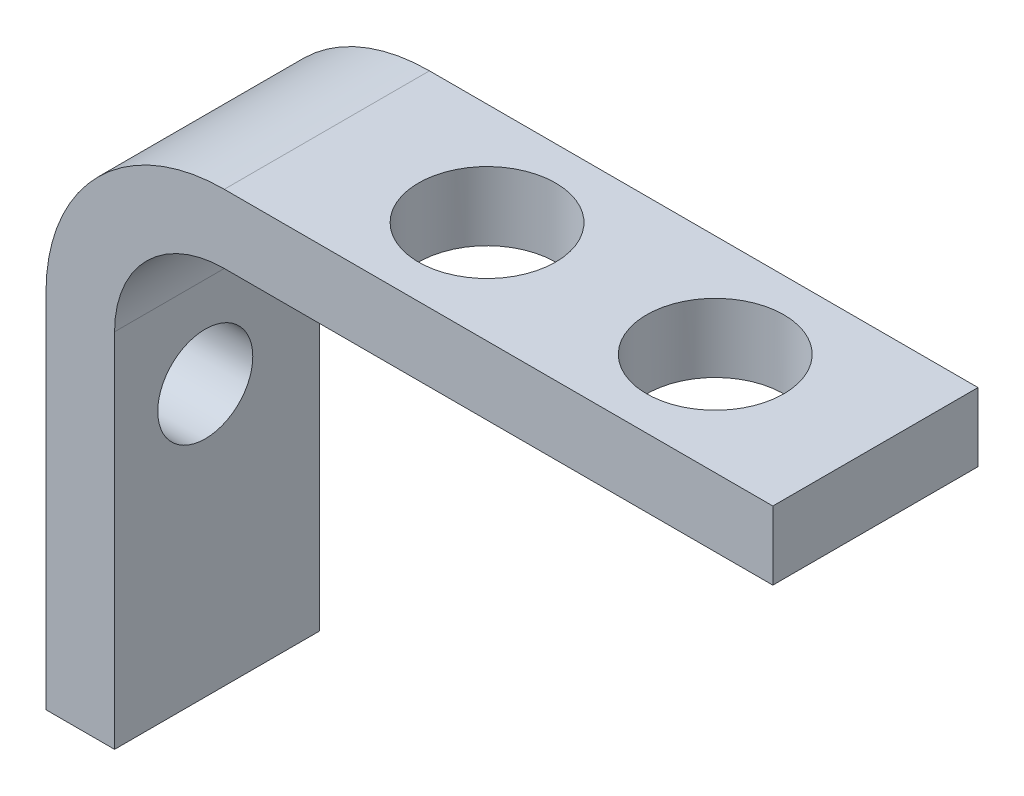
SolidWorks part; units mm, degrees
material "6061 Alloy"
ref_plane "Front Plane" through (0, 0, 0) normal (0, 0, 1) x (1, 0, 0)
ref_plane "Top Plane" through (0, 0, 0) normal (0, 1, 0) x (1, 0, 0)
ref_plane "Right Plane" through (0, 0, 0) normal (1, 0, 0) x (0, 0, -1)
sketch "Sketch1" plane through (0, 0, 0) normal (0, 0, 1) x (1, 0, 0)
  line L0 (0, 0) -> (0, 8.3725)
  line L1 (2.54, 10.9125) -> (15.24, 10.9125)
  line L2 (-1.5875, 0) -> (-1.5875, 8.3725)
  line L3 (2.54, 12.5) -> (15.24, 12.5)
  line L4 (-1.5875, 0) -> (0, 0)
  line L5 (15.24, 10.9125) -> (15.24, 12.5)
  arc A0 (0, 8.3725) -> (2.54, 10.9125) centre (2.54, 8.3725) cw
  arc A1 (-1.5875, 8.3725) -> (2.54, 12.5) centre (2.54, 8.3725) cw
  dimension "D1" = 2.54
  dimension "D2" = 12.7
  dimension "D3" = 12.5
  dimension "D4" = 1.5875
extrude "Boss-Extrude1" add sketch "Sketch1" along normal blind 4.75
sketch "Sketch2" plane through (0, 0, 0) normal (1, 0, 0) x (0, 0, -1)
  line L4 (0, 0) -> (0, 8.3725)
  line L5 (0, 8.3725) -> (-4.75, 8.3725)
  line L6 (-4.75, 8.3725) -> (-4.75, 0)
  line L7 (-4.75, 0) -> (0, 0)
  line L8 (0, 0) -> (0, 8.3725)
  line L9 (0, 8.3725) -> (-4.75, 8.3725)
  line L10 (-4.75, 8.3725) -> (-4.75, 0)
  line L11 (-4.75, 0) -> (0, 0)
  circle A2 centre (-2.65, 6.277) radius 2.0955
  circle A3 centre (-2.65, 6.277) radius 1.1
  dimension "D1" = 0
extrude "Cut-Extrude1" cut sketch "Sketch2" against normal up to next from surface contours A3 region at (0, 6.277, 2.65) starting at face at (0, 4.1863, 2.375)
sketch "Sketch3" plane through (0, 10.9125, 0) normal (0, -1, 0) x (1, 0, 0)
  line L0 (15.24, 2.375) -> (2.54, 2.375) construction
  line L1 (15.24, 4.75) -> (15.24, 0) construction
  line L2 (2.54, 4.75) -> (2.54, 0) construction
  circle A0 centre (6.2484, 2.375) radius 1.5875
  circle A1 centre (11.5316, 2.375) radius 1.5875
  dimension "D1" = 3.7084
  dimension "D3" = 5.2832
  dimension "D2" = 3.7084
extrude "Cut-Extrude2" cut sketch "Sketch3" against normal blind 2.54 contours L0 A0 | L0 A0 | L0 A1 | L0 A1 region at (11.5316, 10.9125, 1.7012) region at (11.5316, 10.9125, 3.0488) region at (6.2484, 10.9125, 1.7012) region at (6.2484, 10.9125, 3.0488)
